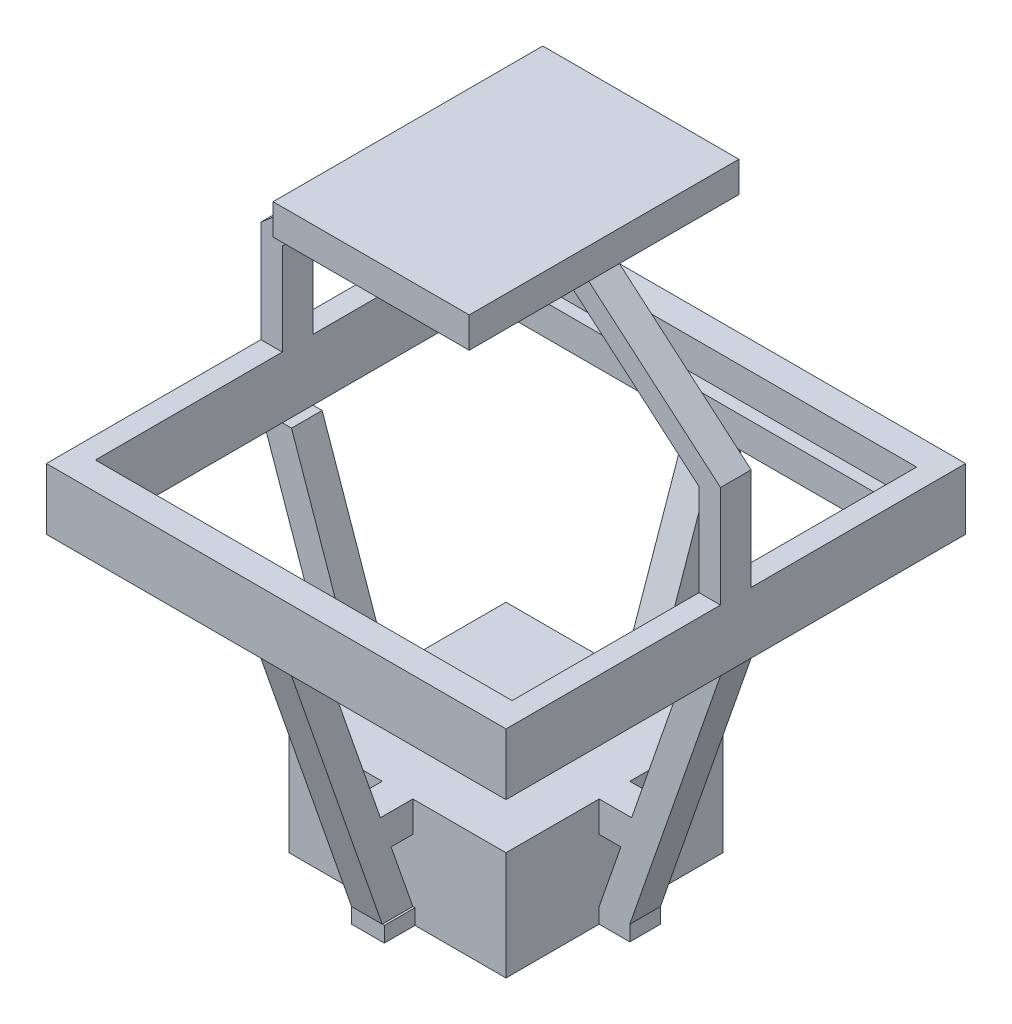
SolidWorks part; units mm, degrees
material "Delrin 2700 NC010, Low Viscosity Acetal Copolymer (SS)"
ref_plane "Front Plane" through (0, 0, 0) normal (0, 0, 1) x (1, 0, 0)
ref_plane "Top Plane" through (0, 0, 0) normal (0, 1, 0) x (1, 0, 0)
ref_plane "Right Plane" through (0, 0, 0) normal (1, 0, 0) x (0, 0, -1)
sketch "Sketch2" plane through (0, 0, 0) normal (0, 1, 0) x (1, 0, 0)
  line L1 (-37.5, 37.5) -> (37.5, 37.5)
  line L2 (-37.5, 37.5) -> (-37.5, -37.5)
  line L3 (-37.5, -37.5) -> (37.5, -37.5)
  line L4 (37.5, 37.5) -> (37.5, -37.5)
  line L5 (-37.5, 37.5) -> (37.5, -37.5) construction
  line L6 (-37.5, -37.5) -> (37.5, 37.5) construction
  point P0 (0, 0)
extrude "Boss-Extrude1" add sketch "Sketch2" along normal blind 5
extrude "Boss-Extrude2" add sketch "Sketch2<2>" against normal blind 5
sketch "Sketch2<2>" plane through (0, 0, 0) normal (0, 1, 0) x (1, 0, 0) same geometry as "Sketch2"
sketch "Sketch4" plane through (0, 5, 0) normal (0, 1, 0) x (1, 0, 0)
  line L1 (-34, 33) -> (34, 33)
  line L2 (-34, 33) -> (-34, -33)
  line L3 (-34, -33) -> (34, -33)
  line L4 (34, 33) -> (34, -33)
  line L5 (-34, 33) -> (34, -33) construction
  line L6 (-34, -33) -> (34, 33) construction
  point P0 (0, 0)
extrude "Cut-Extrude1" cut sketch "Sketch4" against normal blind 5
sketch "Sketch5" plane through (0, 0, 0) normal (0, 1, 0) x (1, 0, 0)
  line L1 (-32, 31) -> (32, 31)
  line L2 (-32, 31) -> (-32, -31)
  line L3 (-32, -31) -> (32, -31)
  line L4 (32, 31) -> (32, -31)
  line L5 (-32, 31) -> (32, -31) construction
  line L6 (-32, -31) -> (32, 31) construction
  point P0 (0, 0)
extrude "Cut-Extrude2" cut sketch "Sketch5" against normal blind 5
ref_plane "Plane1" through (0, 50, 0) normal (0, 1, 0) x (1, 0, 0)
ref_plane "Plane3" through (0, 45, 0) normal (0, 1, 0) x (1, 0, 0)
ref_plane "Plane4" through (0, -50, 0) normal (0, 1, 0) x (1, 0, 0)
sketch "Sketch14" plane through (0, -50, 0) normal (0, 1, 0) x (1, 0, 0)
  line L1 (17.7, 17.7) -> (-17.7, 17.7)
  line L2 (17.7, 17.7) -> (17.7, -17.7)
  line L3 (17.7, -17.7) -> (-17.7, -17.7)
  line L4 (-17.7, 17.7) -> (-17.7, -17.7)
  line L5 (17.7, 17.7) -> (-17.7, -17.7) construction
  line L6 (17.7, -17.7) -> (-17.7, 17.7) construction
  point P0 (0, 0)
extrude "Boss-Extrude9" add sketch "Sketch14" along normal blind 17.7 separate body
sketch "Sketch15" plane through (0, -50, 0) normal (0, -1, 0) x (1, 0, 0)
  line L1 (-12.7, 12.7) -> (12.7, 12.7)
  line L2 (-12.7, 12.7) -> (-12.7, -12.7)
  line L3 (-12.7, -12.7) -> (12.7, -12.7)
  line L4 (12.7, 12.7) -> (12.7, -12.7)
  line L5 (-12.7, 12.7) -> (12.7, -12.7) construction
  line L6 (-12.7, -12.7) -> (12.7, 12.7) construction
  point P0 (0, 0)
extrude "Cut-Extrude3" cut sketch "Sketch15" against normal blind 12.7
extrude "Cut-Extrude6" cut sketch "Sketch32" against normal blind 5
sketch "Sketch32" plane through (0, -32.3, 0) normal (0, 1, 0) x (1, 0, 0)
  circle A0 centre (0, 0) radius 3
sketch "Sketch16" plane through (0, 45, 0) normal (0, 1, 0) x (1, 0, 0)
  line L1 (-16, 22) -> (16, 22)
  line L2 (-16, 22) -> (-16, -22)
  line L3 (-16, -22) -> (16, -22)
  line L4 (16, 22) -> (16, -22)
  line L5 (-16, 22) -> (16, -22) construction
  line L6 (-16, -22) -> (16, 22) construction
  point P0 (0, 0)
extrude "Boss-Extrude10" add sketch "Sketch16" against normal blind 5 separate body
sketch "Sketch18" plane through (0, 45, 0) normal (0, 1, 0) x (1, 0, 0)
  line L21 (16, 22) -> (-16, 22) construction
  line L22 (-5, 22) -> (5, 22)
  line L23 (-5, 22) -> (-5, 31)
  line L24 (-5, 31) -> (5, 31)
  line L25 (5, 22) -> (5, 31)
  line L26 (32, 31) -> (-32, 31) construction
  line L33 (-16, -22) -> (16, -22) construction
  line L34 (-5, -22) -> (5, -22)
  line L35 (-5, -22) -> (-5, -31)
  line L36 (-5, -31) -> (5, -31)
  line L37 (5, -22) -> (5, -31)
  line L38 (-32, -31) -> (32, -31) construction
sketch "Sketch21" plane through (0, 0, 0) normal (0, 0, 1) x (1, 0, 0)
  line L11 (37.5, 5) -> (34, 5)
  line L12 (-34, 5) -> (-37.5, 5)
  line L13 (-34, 5) -> (-37.5, 5)
  line L14 (37.5, 5) -> (34, 5)
  line L15 (16, 40) -> (-16, 40)
  line L16 (16, 40) -> (-16, 40) construction
  line L17 (-37.5, 5) -> (-37.5, 21.6121)
  line L18 (-37.5, 21.6121) -> (-16, 40)
  line L19 (37.5, 5) -> (37.5, 21.6121)
  line L20 (37.5, 21.6121) -> (16, 40)
  line L21 (-34, 5) -> (-34, 20)
  line L22 (-34, 20) -> (-10.6151, 40)
  line L23 (-10.6151, 40) -> (-16, 40)
  line L24 (34, 5) -> (34, 20)
  line L25 (34, 20) -> (10.6151, 40)
  line L26 (10.6151, 40) -> (16, 40)
  line L27 (-22.3075, 30) -> (-24.5824, 32.6599) construction
  line L28 (-16, 40) -> (16, 40) construction
  point P18 (0, 0)
  point P19 (-11.496, 40)
  point P20 (34, 20)
  point P21 (4.3667, 40)
  dimension "D1" = 15
extrude "Boss-Extrude13" add sketch "Sketch21" along normal blind 2.5
extrude "Boss-Extrude14" add sketch "Sketch21<2>" against normal blind 2.5
sketch "Sketch21<2>" plane through (0, 0, 0) normal (0, 0, 1) x (1, 0, 0) same geometry as "Sketch21"
sketch "Sketch31" plane through (0, 45, 0) normal (0, 1, 0) x (1, 0, 0)
  line L0 (0, -52.25) -> (0, 52.25) construction
  circle A0 centre (0, 26) radius 2
  circle A1 centre (0, -26) radius 2
sketch "Sketch27" plane through (0, -50, 0) normal (0, -1, 0) x (-1, 0, 0)
  line L0 (-17.7, -17.7) -> (-17.7, 17.7) construction
  line L1 (-12.2456, -2.5) -> (-34, -2.5) construction
  line L2 (-17.7, -2.5) -> (-22.7, -2.5)
  line L3 (-17.7, -2.5) -> (-17.7, 2.5)
  line L4 (-17.7, 2.5) -> (-22.7, 2.5)
  line L5 (-22.7, -2.5) -> (-22.7, 2.5)
  line L6 (-12.2456, 2.5) -> (-34, 2.5) construction
  line L21 (17.7, 17.7) -> (17.7, -17.7) construction
  line L22 (34, -2.5) -> (12.4348, -2.5) construction
  line L23 (34, 2.5) -> (12.4348, 2.5) construction
  line L26 (17.7, -2.5) -> (22.7, -2.5)
  line L27 (17.7, -2.5) -> (17.7, 2.5)
  line L28 (17.7, 2.5) -> (22.7, 2.5)
  line L29 (22.7, -2.5) -> (22.7, 2.5)
  line L33 (17.7, -17.7) -> (-17.7, -17.7) construction
  line L34 (2.5, -17.7) -> (-2.8444, -17.7)
  line L35 (2.5, -17.7) -> (2.5, -22.7)
  line L36 (2.5, -22.7) -> (-2.8444, -22.7)
  line L37 (-2.8444, -17.7) -> (-2.8444, -22.7)
  line L39 (-17.7, 17.7) -> (17.7, 17.7) construction
  line L44 (2.5, 17.7) -> (-2.5, 17.7)
  line L45 (2.5, 17.7) -> (2.5, 22.7)
  line L46 (2.5, 22.7) -> (-2.5, 22.7)
  line L47 (-2.5, 17.7) -> (-2.5, 22.7)
extrude "Eyebolt Bolt Supports" add sketch "Sketch27" against normal blind 2.5
sketch "Sketch28" plane through (0, 0, 0) normal (0, 0, 1) x (1, 0, 0)
  line L0 (22.7, -47.5) -> (37.5, -5)
  line L1 (37.5, -5) -> (32.5, -5)
  line L2 (-37.5, -5) -> (37.5, -5) construction
  line L3 (32.5, -5) -> (17.7, -47.5)
  line L4 (17.7, -47.5) -> (22.7, -47.5)
  line L5 (-22.7, -47.5) -> (-37.5, -5)
  line L6 (-37.5, -5) -> (-32.5, -5)
  line L7 (-32.5, -5) -> (-17.7, -47.5)
  line L8 (-17.7, -47.5) -> (-22.7, -47.5)
extrude "Boss-Extrude15" add sketch "Sketch28" along normal blind 2.5
extrude "Boss-Extrude16" add sketch "Sketch28<2>" against normal blind 2.5
sketch "Sketch28<2>" plane through (0, 0, 0) normal (0, 0, 1) x (1, 0, 0) same geometry as "Sketch28"
sketch "Sketch30" plane through (0, 0, 0) normal (1, 0, 0) x (0, 0, -1)
  line L0 (22.7, -47.5) -> (37.5, -5)
  line L1 (37.5, -5) -> (32.5, -5)
  line L2 (2.5, -5) -> (37.5, -5) construction
  line L3 (22.7, -47.5) -> (17.7, -47.5)
  line L4 (17.7, -47.5) -> (32.5, -5)
  line L5 (-37.5, -5) -> (-22.7, -47.5)
  line L7 (-22.7, -47.5) -> (-17.7, -47.5)
  line L8 (-17.7, -47.5) -> (-32.5, -5)
  line L9 (-37.5, -5) -> (-2.5, -5) construction
  line L10 (-32.5, -5) -> (-37.5, -5)
extrude "Boss-Extrude17" add sketch "Sketch30" along normal blind 2.5
extrude "Boss-Extrude18" add sketch "Sketch30<2>" against normal blind 2.5
sketch "Sketch30<2>" plane through (0, 0, 0) normal (1, 0, 0) x (0, 0, -1) same geometry as "Sketch30"
sketch "Sketch33" plane through (0, -32.3, 0) normal (0, 1, 0) x (1, 0, 0)
  line L0 (17.7, -17.7) -> (17.7, 17.7) construction
  line L1 (17.7, 2.5) -> (24, 2.5)
  line L2 (17.7, 2.5) -> (17.7, -2.5)
  line L3 (17.7, -2.5) -> (24, -2.5)
  line L4 (24, 2.5) -> (24, -2.5)
  line L5 (17.7, 17.7) -> (-17.7, 17.7) construction
  line L6 (2.5, 17.7) -> (-2.5, 17.7)
  line L7 (2.5, 17.7) -> (2.5, 24)
  line L8 (2.5, 24) -> (-2.5, 24)
  line L9 (-2.5, 17.7) -> (-2.5, 24)
  line L10 (-17.7, 17.7) -> (-17.7, -17.7) construction
  line L11 (-17.7, 2.5) -> (-24, 2.5)
  line L12 (-17.7, 2.5) -> (-17.7, -2.5)
  line L13 (-17.7, -2.5) -> (-24, -2.5)
  line L14 (-24, 2.5) -> (-24, -2.5)
  line L16 (-2.5, -17.7) -> (2.5, -17.7)
  line L17 (-2.5, -17.7) -> (-2.5, -24)
  line L18 (-2.5, -24) -> (2.5, -24)
  line L19 (2.5, -17.7) -> (2.5, -24)
extrude "Eyebolt Mini Supports " add sketch "Sketch33" against normal blind 5
sketch "Sketch34" plane through (0, 0, 0) normal (0, 1, 0) x (1, 0, 0)
  line L0 (-34, 33) -> (-34, -33) construction
  line L1 (-32, 31) -> (-34, 31)
  line L2 (-32, 31) -> (-32, -31)
  line L3 (-32, -31) -> (-34, -31)
  line L4 (-34, 31) -> (-34, -31)
  line L5 (34, -33) -> (34, -2.5) construction
  line L6 (32, 31) -> (34, 31)
  line L7 (32, 31) -> (32, -30.1823)
  line L8 (32, -30.1823) -> (34, -30.1823)
  line L9 (34, 31) -> (34, -30.1823)
  line L10 (-32, -31) -> (32, -31) construction
extrude "Cut-Extrude7" cut sketch "Sketch34" along direction (0, 1, 0) on the side against the normal up to surface (5 mm away) up to face at (0, -5, 0)
